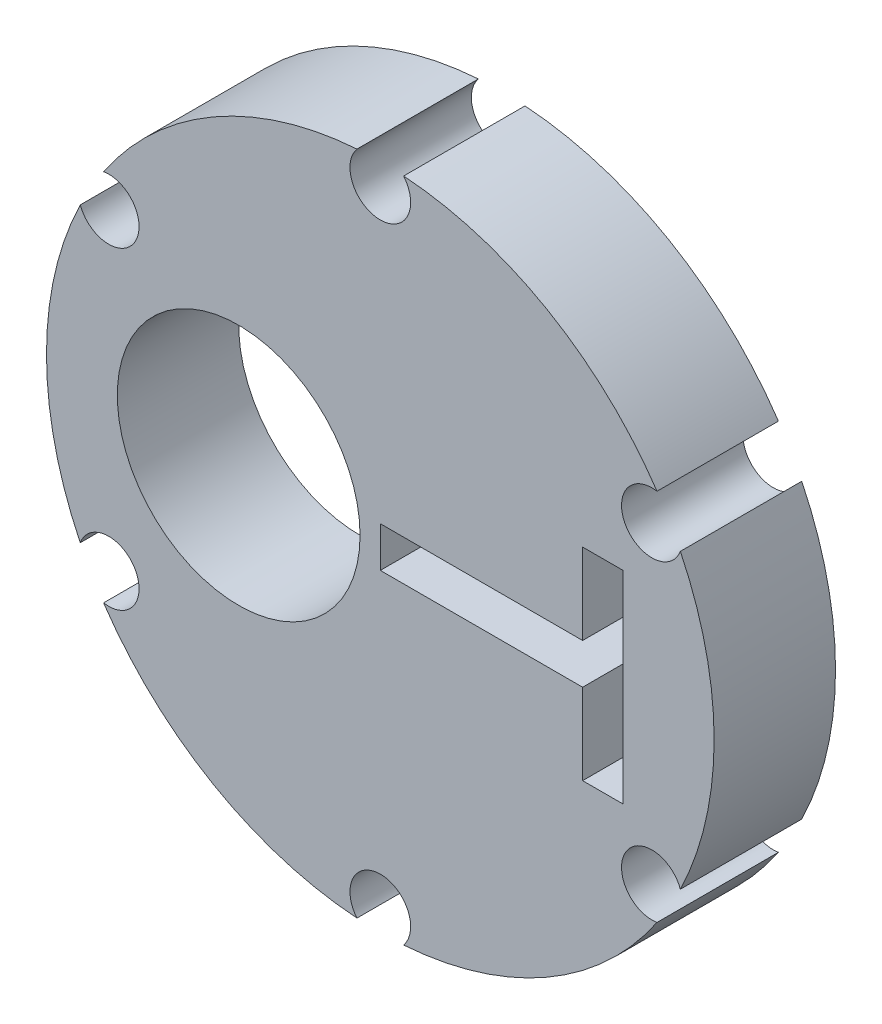
SolidWorks part; units mm, degrees
material "ABS"
ref_plane "Front Plane" through (0, 0, 0) normal (0, 0, 1) x (1, 0, 0)
ref_plane "Top Plane" through (0, 0, 0) normal (0, 1, 0) x (1, 0, 0)
ref_plane "Right Plane" through (0, 0, 0) normal (1, 0, 0) x (0, 0, -1)
sketch "Sketch1" plane through (0, 0, 0) normal (0, 0, 1) x (1, 0, 0)
  circle A0 centre (0, 0) radius 16.5
  dimension "D1" = 33
extrude "Boss-Extrude1" add sketch "Sketch1" along normal blind 6
sketch "Sketch2" plane through (0, 0, 6) normal (0, 0, 1) x (1, 0, 0)
  circle A0 centre (0, 15.5) radius 1.5
  circle A1 centre (13.4234, 7.75) radius 1.5
  circle A2 centre (13.4234, -7.75) radius 1.5
  circle A3 centre (0, -15.5) radius 1.5
  circle A4 centre (-13.4234, -7.75) radius 1.5
  circle A5 centre (-13.4234, 7.75) radius 1.5
  point P15 (0, 0)
  dimension "D1" = 3
  dimension "D2" = 15.5
  dimension "D3" = 6
extrude "Cut-Extrude1" cut sketch "Sketch2" against normal through all
sketch "Sketch3" plane through (0, 0, 6) normal (0, 0, 1) x (1, 0, 0)
  line L0 (-7, 0) -> (0, 0) construction
  circle A0 centre (-7, 0) radius 6
  dimension "D1" = 12
  dimension "D3" = 7
extrude "Cut-Extrude2" cut sketch "Sketch3" against normal through all
sketch "Sketch5" plane through (0, 0, 6) normal (0, 0, 1) x (1, 0, 0)
  line L1 (12, 5) -> (10, 5)
  line L2 (12, 5) -> (12, -5)
  line L3 (12, -5) -> (10, -5)
  line L4 (10, 5) -> (10, 1)
  line L5 (10, -1) -> (10, -5)
  line L6 (0, 1) -> (10, 1)
  line L7 (0, 1) -> (0, -1)
  line L8 (0, -1) -> (10, -1)
  point P10 (0, 0)
  dimension "D1" = 10
  dimension "D2" = 2
extrude "Cut-Extrude3" cut sketch "Sketch5" against normal through all
equation "\"smallPulleyTeeth\"= 30"
equation "\"largePulleyTeeth\"= 30"
equation "\"eighthThick\"= 3.0mm"
equation "\"sixteenthThick\"= 1.7mm"
equation "\"wheelEighthThick\"=3.0mm"
equation "\"quarterThick\"=6.0mm"
equation "\"OD\"= 145mm"
equation "\"puckAngle\"= 60.5deg"
equation "\"puckDiam\"= 76.5mm"
equation "\"axlePress\"= 5.9mm"
equation "\"D1@Boss-Extrude1\"=\"quarterThick\""
